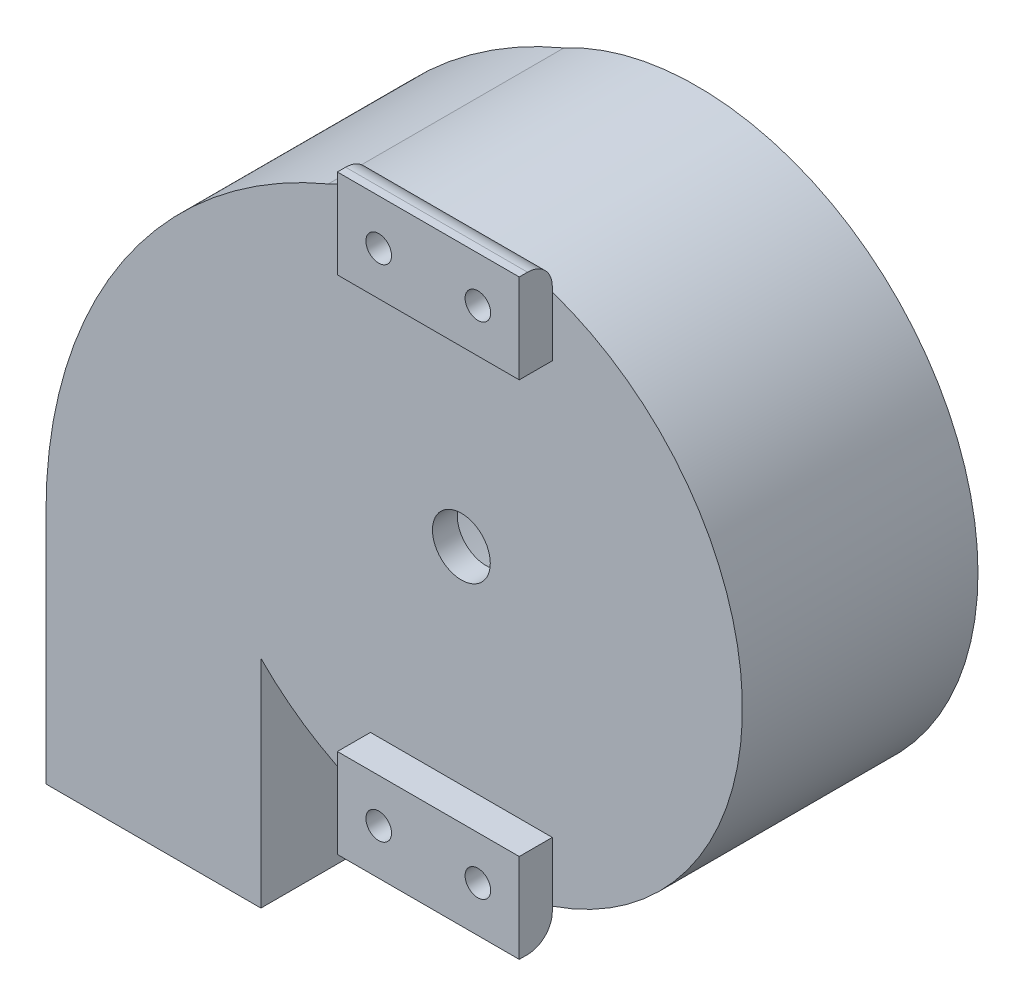
SolidWorks part; units mm, degrees
ref_plane "Front Plane" through (0, 0, 0) normal (0, 0, 1) x (1, 0, 0)
ref_plane "Top Plane" through (0, 0, 0) normal (0, 1, 0) x (1, 0, 0)
ref_plane "Right Plane" through (0, 0, 0) normal (1, 0, 0) x (0, 0, -1)
sketch "Sketch1" plane through (0, 0, 0) normal (0, 0, 1) x (1, 0, 0)
  circle A0 centre (0, 0) radius 31.25
  circle A1 centre (0, 0) radius 34
extrude "Boss-Extrude1" add sketch "Sketch1" along normal blind 25.5
sketch "Sketch2" plane through (0, 0, 25.5) normal (0, 0, 1) x (1, 0, 0)
  circle A1 centre (0, 0) radius 34
extrude "Boss-Extrude2" add sketch "Sketch2" along normal blind 3
sketch "Sketch3" plane through (0, 0, 25.5) normal (0, 0, -1) x (-1, 0, 0)
  line L12 (24.25, -50) -> (50.25, -50)
  line L14 (50.25, -50) -> (50.25, -21.3681)
  line L17 (0, 34) -> (0, 31.25)
  line L18 (24.25, -50) -> (24.25, -19.7104)
  circle A0 centre (0, 0) radius 31.25 construction
  arc A9 (50.25, -21.3681) -> (0, 34) centre (-5.3787, -21.3681) ccw
  circle A10 centre (0, 0) radius 34 construction
  arc A15 (0, 31.25) -> (24.25, -19.7104) centre (0, 0) cw
sketch "Sketch5" plane through (0, 0, 28.5) normal (0, 0, 1) x (1, 0, 0)
  circle A0 centre (0, 0) radius 3.5
extrude "Cut-Extrude3" cut sketch "Sketch5" against normal blind 51
extrude "Boss-Extrude9" add sketch "Sketch3" along normal up to surface (25.5 mm away) from surface up to face at (34, 0, 0) starting at face at (3.5, 0, 28.5)
ref_plane "Plane1" through (0, 0, 14.25) normal (0, 0, -1) x (-1, 0, 0)
sketch "Sketch28" plane through (0, 0, 14.25) normal (0, 0, -1) x (-1, 0, 0)
  line L0 (37.25, -50) -> (37.25, -21.3681)
  line L1 (24.25, -50) -> (50.25, -50) construction
  arc A3 (37.25, -21.3681) -> (6.0625, 19.5421) centre (-5.1758, -21.3681) ccw
sweep "Cut-Sweep6" cut path "Sketch28" circular profile diameter 22 parameters "D3"=22
sketch "Sketch219" plane through (0, -50, 0) normal (0, -1, 0) x (1, 0, 0)
  circle A0 centre (-37.25, 14.25) radius 12
extrude "Cut-Extrude10" cut sketch "Sketch219" against normal blind 20
sketch "Sketch227" plane through (0, 0, 28.5) normal (0, 0, 1) x (1, 0, 0)
  line L0 (11, 35.75) -> (11, 14.1846) construction
  line L1 (-11, 35.75) -> (11, 35.75)
  line L2 (-11, 35.75) -> (-11, 24.9673)
  line L3 (-11, 24.9673) -> (11, 24.9673)
  line L4 (11, 35.75) -> (11, 24.9673)
  line L5 (11, -14.1846) -> (11, -35.75) construction
  line L6 (-11, -35.75) -> (11, -35.75)
  line L7 (-11, -35.75) -> (-11, -24.9673)
  line L8 (-11, -24.9673) -> (11, -24.9673)
  line L9 (11, -35.75) -> (11, -24.9673)
  circle A0 centre (-6, 30.25) radius 1.55
  circle A1 centre (6, 30.25) radius 1.55
  circle A2 centre (-6, -30.25) radius 1.55
  circle A3 centre (6, -30.25) radius 1.55
extrude "Boss-Extrude11" add sketch "Sketch227" along normal blind 4
fillet "Fillet1" radius 3 1 edges at (0, 35.75, 28.5) type face fillet first side face at (0, 34.4179, 28.5) second side face at (0, 35.75, 30.5)
fillet "Fillet2" radius 3 1 edges at (0, -35.75, 28.5) type face fillet first side face at (0, -35.75, 30.5) second side face at (0, -34.4179, 28.5)
